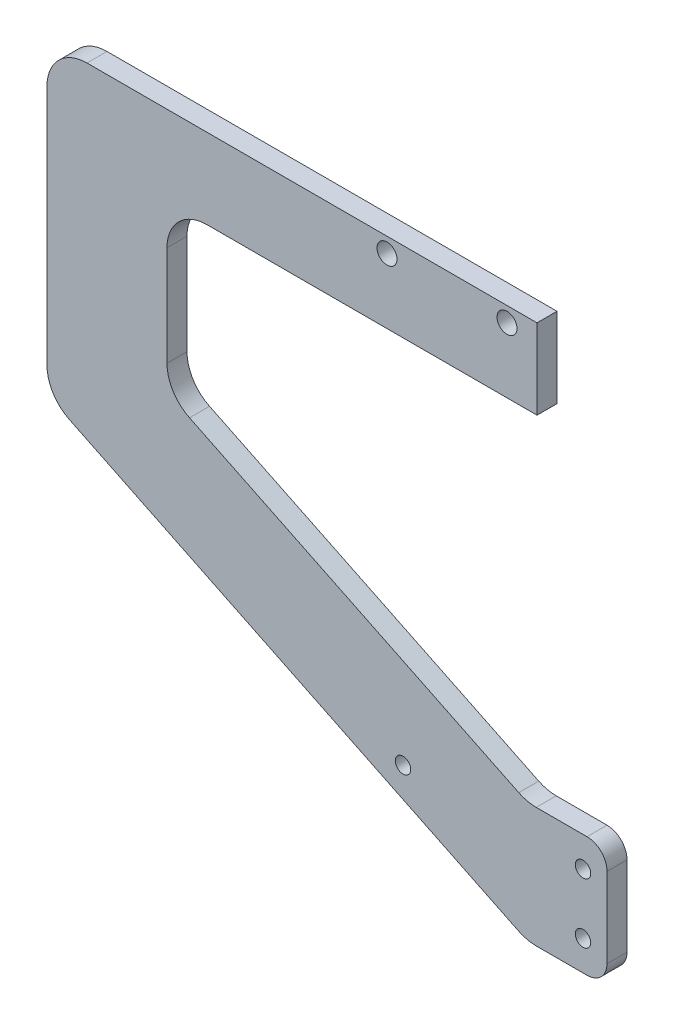
SolidWorks part; units mm, degrees
material "6061 Alloy"
ref_plane "Front Plane" through (0, 0, 0) normal (0, 0, 1) x (1, 0, 0)
ref_plane "Top Plane" through (0, 0, 0) normal (0, 1, 0) x (1, 0, 0)
ref_plane "Right Plane" through (0, 0, 0) normal (1, 0, 0) x (0, 0, -1)
sketch "Sketch1" plane through (0, 0, 0) normal (0, 0, 1) x (1, 0, 0)
  line L0 (0, 0) -> (0, 38.1)
  line L1 (0, 38.1) -> (-25.4, 38.1)
  line L2 (-139.7, 101.6) -> (-139.7, 133.35)
  line L3 (-127, 146.05) -> (-22.225, 146.05)
  line L4 (-22.225, 146.05) -> (-22.225, 171.45)
  line L5 (-22.225, 171.45) -> (-165.1, 171.45)
  line L6 (-177.8, 158.75) -> (-177.8, 82.0173)
  line L7 (0, 0) -> (-25.4, 0)
  line L8 (-170.6515, 70.5949) -> (-25.4, 0)
  line L9 (0, 19.05) -> (25.4, 19.05) construction
  line L10 (25.4, 19.05) -> (25.4, 120.65) construction
  line L11 (25.4, 120.65) -> (-127, 120.65) construction
  line L12 (-25.4, 38.1) -> (-132.5515, 90.1776)
  line L13 (0, 19.05) -> (-7.62, 19.05) construction
  line L14 (-7.62, 28.575) -> (-7.62, 9.525) construction
  line L15 (-7.62, 28.575) -> (-64.77, 28.575) construction
  line L16 (-69.85, 166.6875) -> (-31.75, 166.6875) construction
  line L17 (-50.8, 166.6875) -> (-50.8, 120.65) construction
  line L18 (-127, 120.65) -> (-127, 101.6) construction
  arc A0 (-177.8, 82.0173) -> (-170.6515, 70.5949) centre (-165.1, 82.0173) ccw
  arc A1 (-165.1, 171.45) -> (-177.8, 158.75) centre (-165.1, 158.75) ccw
  arc A2 (-139.7, 133.35) -> (-127, 146.05) centre (-127, 133.35) cw
  arc A3 (-132.5515, 90.1776) -> (-139.7, 101.6) centre (-127, 101.6) cw
  circle A7 centre (-31.75, 166.6875) radius 3.175 construction
  circle A8 centre (-69.85, 166.6875) radius 3.175 construction
  point P26 (-50.8, 166.6875)
  point P28 (-50.8, 120.65)
  dimension "D9" = 12.7
  dimension "D10" = 12.7
  dimension "D22" = 6.35
  dimension "D1" = 38.1
  dimension "D3" = 38.1
  dimension "D4" = 25.4
  dimension "D5" = 19.05
  dimension "D6" = 25.4
  dimension "D7" = 57.15
  dimension "D11" = 25.4
  dimension "D12" = 101.6
  dimension "D13" = 152.4
  dimension "D14" = 25.4
  dimension "D15" = 19.05
  dimension "D17" = 7.62
  dimension "D19" = 4.7625
  dimension "D20" = 38.1
  dimension "D21" = 9.525
extrude "Boss-Extrude1" add sketch "Sketch1" along normal blind 6.35
hole_wizard "1/4 (0.25) Diameter Hole1" positions "Sketch3" profile "Sketch2" hole size "1/4" standard "ANSI Inch"
sketch "Sketch3" plane through (0, 0, 6.35) normal (0, 0, 1) x (1, 0, 0)
  line L0 (-69.85, 166.6875) -> (-22.225, 166.6875) construction
  line L1 (-22.225, 146.05) -> (-22.225, 171.45) construction
  line L3 (-22.225, 171.45) -> (-165.1, 171.45) construction
  point P4 (-69.85, 166.6875)
  point P6 (-31.75, 166.6875)
  dimension "D1" = 9.525
  dimension "D2" = 38.1
  dimension "D3" = 4.7625
sketch "Sketch2" plane through (-69.85, 166.6875, 6.35) normal (1, 0, 0) x (0, -1, 0)
  line L0 (0, 0) -> (0, 11.5597)
  line L1 (0, 11.5597) -> (3.175, 9.652)
  line L2 (3.175, 9.652) -> (3.175, 0)
  line L5 (3.175, 0) -> (0, 0)
  line L10 (0, 11.5597) -> (-3.175, 9.652) construction
  line L11 (0, -6.35) -> (0, 107.95) construction
  dimension "Hole Dia." = 6.35
  dimension "Hole Depth" = 9.652
  dimension "Drill Angle" = 118
hole_wizard "#10 (0.1935) Diameter Hole1" positions "Sketch5" profile "Sketch4" hole size "#10" standard "ANSI Inch"
sketch "Sketch5" plane through (0, 0, 6.35) normal (0, 0, 1) x (1, 0, 0)
  line L0 (-7.62, 28.575) -> (-7.62, 9.525) construction
  line L2 (0, 19.05) -> (-7.62, 19.05) construction
  line L3 (0, 0) -> (0, 38.1) construction
  line L6 (-64.77, 28.575) -> (-7.62, 28.575) construction
  point P0 (-7.62, 28.575)
  point P2 (-7.62, 9.525)
  point P18 (-64.77, 28.575)
  dimension "D1" = 19.05
  dimension "D2" = 7.62
  dimension "D3" = 57.15
sketch "Sketch4" plane through (-7.62, 28.575, 6.35) normal (1, 0, 0) x (0, -1, 0)
  line L0 (0, 0) -> (0, 11.1286)
  line L1 (0, 11.1286) -> (2.4574, 9.652)
  line L2 (2.4574, 9.652) -> (2.4574, 0)
  line L5 (2.4574, 0) -> (0, 0)
  line L10 (0, 11.1286) -> (-2.4575, 9.652) construction
  line L11 (0, -6.35) -> (0, 107.95) construction
  dimension "Hole Dia." = 4.9149
  dimension "Hole Depth" = 9.652
  dimension "Drill Angle" = 118
fillet "Fillet1" radius 12.7 2 edges at (-25.4, 0, 3.175) (-25.4, 38.1, 3.175)
fillet "Fillet2" radius 6.35 2 edges at (0, 0, 3.175) (0, 38.1, 3.175)
